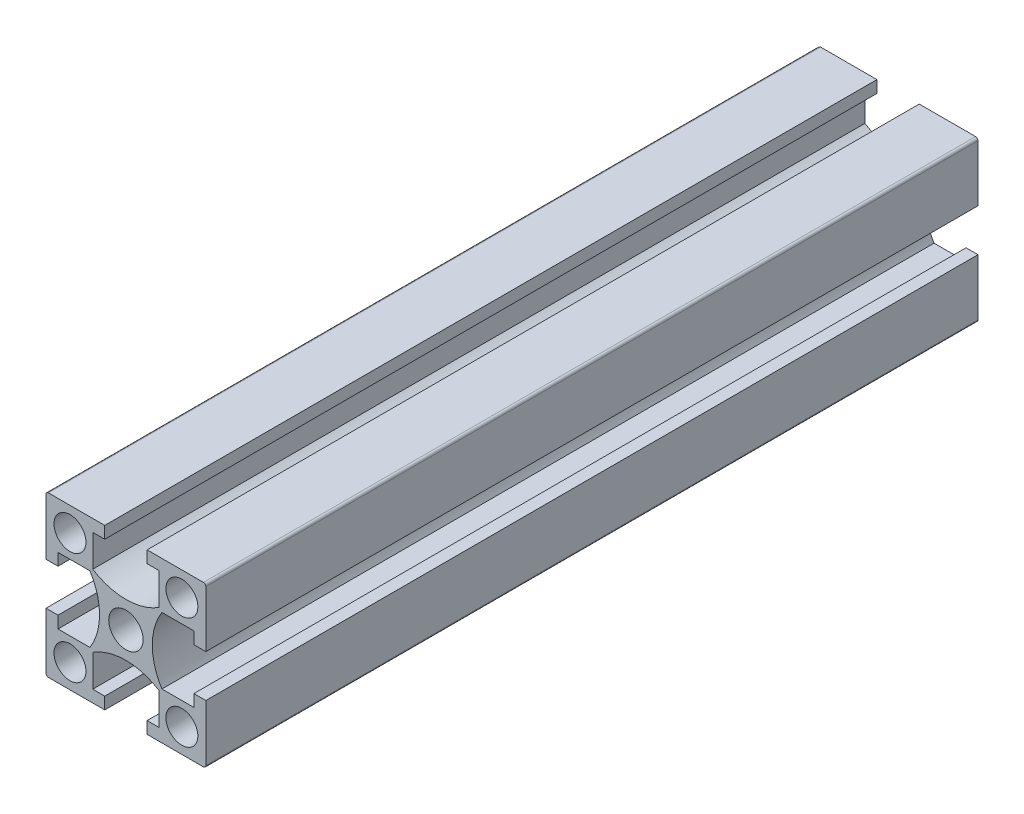
SolidWorks part; units mm, degrees
material "3.0255 (EN-AW 1350A)"
ref_plane "정면" through (0, 0, 0) normal (0, 0, 1) x (1, 0, 0)
ref_plane "윗면" through (0, 0, 0) normal (0, 1, 0) x (1, 0, 0)
ref_plane "우측면" through (0, 0, 0) normal (1, 0, 0) x (0, 0, -1)
sketch "스케치1" plane through (0, 0, 0) normal (0, 0, 1) x (1, 0, 0)
  line L0 (0, 32.0265) -> (0, -31.6588) construction
  line L1 (-10, 10) -> (-10, -10)
  line L2 (-10, 10) -> (10, 10)
  line L3 (-10, 2.65) -> (-8.5, 2.65)
  line L4 (13.6618, 0) -> (-11.6993, 0) construction
  line L5 (-8.5, 2.65) -> (-8.5, 4.15)
  line L6 (-8.5, 4.15) -> (-4.5032, 4.15)
  line L7 (-10, -2.65) -> (-8.5, -2.65)
  line L8 (-8.5, -2.65) -> (-8.5, -4.15)
  line L9 (-8.5, -4.15) -> (-4.5032, -4.15)
  line L10 (-10, -10) -> (10, -10)
  line L11 (10, 10) -> (10, -10)
  circle A0 centre (-7, 7) radius 2
  circle A1 centre (-7, -7) radius 2
  arc A2 (-4.5032, 4.15) -> (-4.5032, -4.15) centre (-11.0587, 0) cw
  circle A3 centre (0, 0) radius 2.15
  circle A4 centre (7, 7) radius 2
  circle A5 centre (7, -7) radius 2
  point P21 (-10, 0)
  point P23 (-3.3, 0)
  point P31 (0, -10)
  point P32 (0, 10)
  dimension "D3" = 4
  dimension "D9" = 6.7
  dimension "D10" = 4.3
  dimension "D11" = 7.7587
  dimension "D1" = 20
  dimension "D2" = 20
  dimension "D4" = 14
  dimension "D5" = 14
  dimension "D6" = 5.3
  dimension "D7" = 8.3
  dimension "D8" = 1.5
extrude "보스-돌출1" add sketch "스케치1" along normal blind 293 contours A0 | A4 | A3 | A5 | A1 | A2 L6 L5 L3 L1 L7 L8 L9 | L2 L11 L10 L1 region at (-6.6069, 0, 0) region at (-7, 7, 0) region at (-7, -7, 0) region at (0, 0, 0) region at (7, 7, 0) region at (7, -7, 0)
extrude "컷-돌출1" cut sketch "스케치1<3>" along normal up to next contours A2 L6 L5 L3 L1 L7 L8 L9 region at (-6.6069, 0, 0)
sketch "스케치1<3>" plane through (0, 0, 0) normal (0, 0, 1) x (1, 0, 0) same geometry as "스케치1"
pattern_circular "원형 패턴1" count 4 over 360 about axis through (0, 0, 293) along (0, 0, -1) of "컷-돌출1" reverse direction yes
fillet "필렛1" radius 0.3 4 edges at (10, -10, 146.5) (-10, -10, 146.5) (-10, 10, 146.5) (10, 10, 146.5)
sketch "스케치2" plane through (0, 0, 0) normal (1, 0, 0) x (0, 0, -1)
  circle A0 centre (-25, 0) radius 2.5
  dimension "D1" = 5
  dimension "D2" = 25
extrude "컷-돌출2" cut sketch "스케치2" against normal through all both and the other way through all
sketch "스케치4" plane through (0, 10, 0) normal (0, 1, 0) x (1, 0, 0)
  line L0 (0, -55) -> (0, 55) construction
  line L3 (-2.65, -106.62) -> (2.65, -106.62) construction
  line L4 (-2.65, -293) -> (-2.65, 0) construction
  line L5 (2.65, -293) -> (2.65, 0) construction
  line L6 (2.65, 0) -> (9.7, 0) construction
  circle A1 centre (0, -282) radius 2.5
  circle A2 centre (0, -127.62) radius 2.5
  circle A3 centre (0, -85.62) radius 2.5
  dimension "D1" = 21
  dimension "D2" = 282
  dimension "D3" = 106.62
  dimension "D4" = 21
extrude "컷-돌출3" cut sketch "스케치4" against normal through all
sketch "스케치6" plane through (0, 10, 0) normal (0, 1, 0) x (1, 0, 0)
  line L0 (0, -55) -> (0, 55) construction
  line L1 (4.15, 0) -> (-4.15, 0) construction
  line L3 (-9.7, 0) -> (-2.65, 0) construction
  circle A0 centre (0, -236.9) radius 2.15
  circle A1 centre (0, -184.9) radius 2.15
  circle A2 centre (0, -10.15) radius 1.9797
  circle A3 centre (0, -62.15) radius 2.15
  dimension "D1" = 184.9
  dimension "D2" = 236.9
  dimension "D4" = 52
  dimension "D3" = 10.15
extrude "컷-돌출4" cut sketch "스케치6" against normal through all
sketch "스케치7" plane through (0, 10, 0) normal (0, 1, 0) x (1, 0, 0)
  line L0 (-10, -96.62) -> (10, -96.62)
  line L1 (-10, -293) -> (-10, 0) construction
  line L2 (10, 0) -> (10, -293) construction
  line L3 (-10, -96.62) -> (-10, -293)
  line L4 (-10, -293) -> (10, -293)
  line L5 (10, -293) -> (10, -96.62)
  circle A0 centre (0, -85.62) radius 2.5 construction
  dimension "D1" = 11
extrude "컷-돌출5" cut sketch "스케치7" against normal through all
